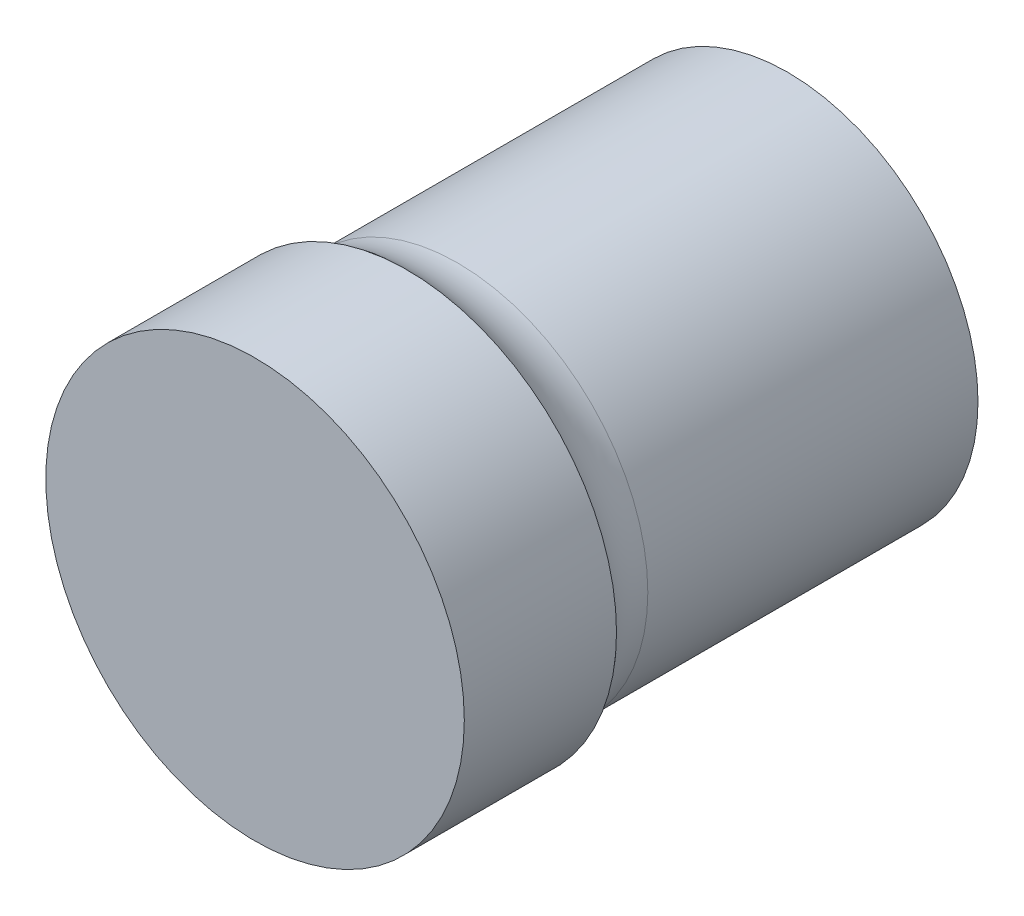
SolidWorks part; units mm, degrees
ref_plane "Piano frontale" through (0, 0, 0) normal (0, 0, 1) x (1, 0, 0)
ref_plane "Piano superiore" through (0, 0, 0) normal (0, 1, 0) x (1, 0, 0)
ref_plane "Piano destro" through (0, 0, 0) normal (1, 0, 0) x (0, 0, -1)
sketch "Schizzo1" plane through (0, 0, 0) normal (0, 0, 1) x (1, 0, 0)
  circle A0 centre (0, 0) radius 1.5
  circle A1 centre (0, 0) radius 2.5
  dimension "D1" = 3
  dimension "D2" = 5
extrude "Estrusione-Estrusione1" add sketch "Schizzo1" along normal blind 5
sketch "Schizzo2" plane through (0, 0, 5) normal (0, 0, 1) x (1, 0, 0)
  circle A0 centre (0, 0) radius 2.75
  dimension "D1" = 5.5
extrude "Estrusione-Estrusione2" add sketch "Schizzo2" along normal blind 2
fillet "Raccordo1" radius 1 1 edges at (2.5, 0, 5)
